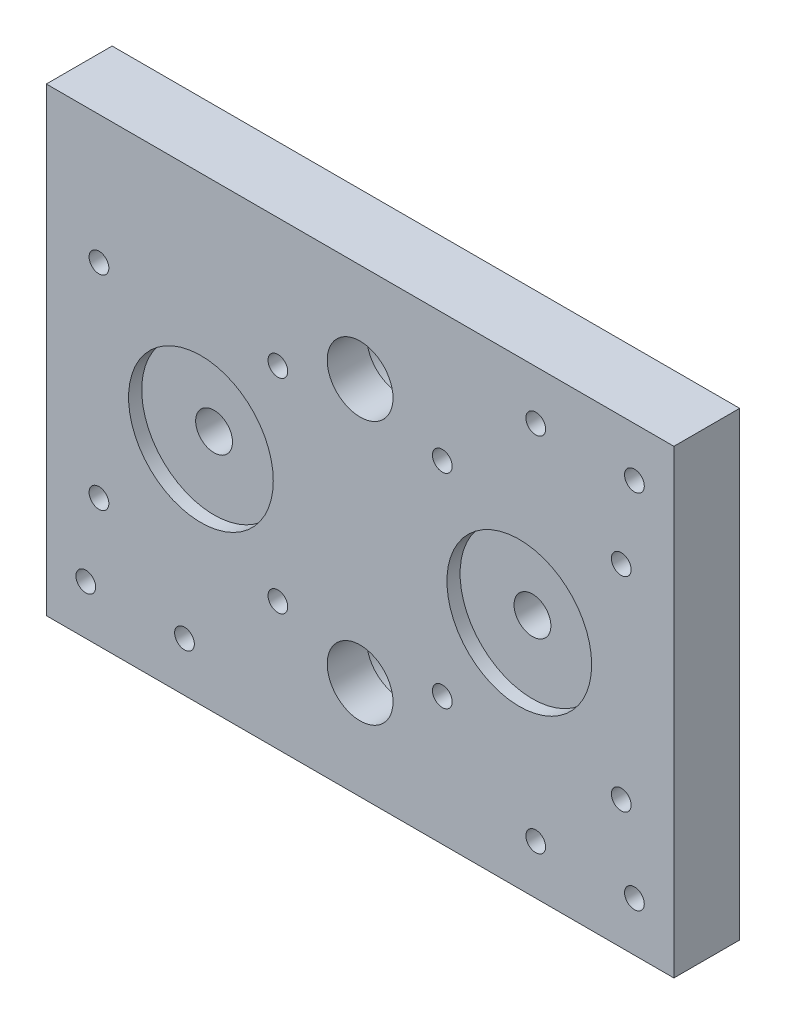
SolidWorks part; units mm, degrees
ref_plane "Front Plane" through (0, 0, 0) normal (0, 0, 1) x (1, 0, 0)
ref_plane "Top Plane" through (0, 0, 0) normal (0, 1, 0) x (1, 0, 0)
ref_plane "Right Plane" through (0, 0, 0) normal (1, 0, 0) x (0, 0, -1)
sketch "Sketch1" plane through (0, 0, 0) normal (0, 0, 1) x (1, 0, 0)
  line L0 (0, 0) -> (0, 40) construction
  line L2 (12.5, -15) -> (-12.5, -15)
  line L3 (12.5, -15) -> (12.5, 55)
  line L4 (12.5, 55) -> (-12.5, 55)
  line L5 (-12.5, -15) -> (-12.5, 55)
  line L6 (12.5, -15) -> (-12.5, 55) construction
  line L7 (12.5, 55) -> (-12.5, -15) construction
  circle A0 centre (0, 40) radius 7.9375
  circle A1 centre (0, 0) radius 7.9375
  point P5 (0, 20)
  dimension "D2" = 15.875
  dimension "D1" = 40
  dimension "D3" = 70
  dimension "D4" = 25
extrude "Boss-Extrude1" add sketch "Sketch1" along normal blind 10
sketch "Sketch2" plane through (0, 0, 10) normal (0, 0, 1) x (1, 0, 0)
  line L0 (12.5, 55) -> (-12.5, 55) construction
  line L1 (-47.7, 55) -> (-8.2, 55)
  line L3 (-47.7, -15) -> (-8.2, -15)
  line L4 (-8.2, 55) -> (-8.2, 36.9142)
  line L5 (-39.7, 35.5) -> (-8.7, 4.5) construction
  line L6 (-39.7, 4.5) -> (-8.7, 35.5) construction
  line L7 (-12.5, -15) -> (12.5, -15) construction
  line L8 (-8.2, 34.0858) -> (-8.2, 5.9142)
  line L9 (0, 55) -> (0, -15) construction
  line L10 (-8.7, 4.5) -> (-39.7, 4.5) construction
  line L11 (-8.7, 4.5) -> (-8.7, 35.5) construction
  line L12 (-8.7, 35.5) -> (-39.7, 35.5) construction
  line L13 (-39.7, 4.5) -> (-39.7, 35.5) construction
  line L14 (-8.7, 4.5) -> (-39.7, 35.5) construction
  line L15 (-8.7, 35.5) -> (-39.7, 4.5) construction
  line L16 (8.7, 35.5) -> (39.7, 4.5) construction
  line L17 (8.7, 4.5) -> (39.7, 35.5) construction
  line L18 (39.7, 4.5) -> (39.7, 35.5) construction
  line L19 (8.7, 35.5) -> (39.7, 35.5) construction
  line L20 (8.7, 4.5) -> (8.7, 35.5) construction
  line L21 (8.7, 4.5) -> (39.7, 4.5) construction
  line L22 (39.7, 4.5) -> (8.7, 35.5) construction
  line L23 (39.7, 35.5) -> (8.7, 4.5) construction
  line L24 (8.2, 55) -> (8.2, 36.9142)
  line L25 (47.7, -15) -> (8.2, -15)
  line L27 (47.7, 55) -> (8.2, 55)
  line L28 (-47.7, 55) -> (-47.7, -15)
  line L29 (47.7, 55) -> (47.7, -15)
  line L31 (-8.2, 3.0858) -> (-8.2, -15)
  line L32 (8.2, 3.0858) -> (8.2, -15)
  line L33 (8.2, 34.0858) -> (8.2, 5.9142)
  circle A0 centre (-39.7, 35.5) radius 1.5
  arc A1 (-8.2, 36.9142) -> (-8.2, 34.0858) centre (-8.7, 35.5) ccw
  arc A2 (-8.2, 5.9142) -> (-8.2, 3.0858) centre (-8.7, 4.5) ccw
  circle A3 centre (-39.7, 4.5) radius 1.5
  circle A4 centre (39.7, 4.5) radius 1.5
  arc A5 (8.2, 5.9142) -> (8.2, 3.0858) centre (8.7, 4.5) cw
  arc A6 (8.2, 36.9142) -> (8.2, 34.0858) centre (8.7, 35.5) cw
  circle A7 centre (39.7, 35.5) radius 1.5
  circle A8 centre (-24.2, 20) radius 2.8
  circle A9 centre (24.2, 20) radius 2.8
  point P0 (-24.2, 20)
  point P11 (-24.2, 20)
  point P34 (24.2, 20)
  dimension "D2" = 3
  dimension "D3" = 5.6
  dimension "D1" = 31
  dimension "D4" = 0.5
  dimension "D5" = 8
  dimension "D6" = 8.2
extrude "Boss-Extrude2" add sketch "Sketch2" against normal up to surface (10 mm away) up to face at (0, 20, 0)
sketch "Sketch6" plane through (0, 0, 10) normal (0, 0, 1) x (1, 0, 0)
  circle A0 centre (-12.5, 35.5) radius 1.5
  circle A1 centre (12.5, 35.5) radius 1.5
  circle A2 centre (-12.5, 4.5) radius 1.5
  circle A3 centre (12.5, 4.5) radius 1.5
  circle A5 centre (-39.7, 35.5) radius 1.5 construction
extrude "Cut-Extrude3" cut sketch "Sketch6" against normal up to surface (10 mm away) up to face at (0, 20, 0)
sketch "Sketch3" plane through (0, 0, 10) normal (0, 0, 1) x (1, 0, 0)
  circle A0 centre (0, 40) radius 7.9375
  circle A1 centre (0, 0) radius 7.9375
  circle A2 centre (0, 40) radius 7.9375 construction
  circle A3 centre (0, 40) radius 5
  circle A4 centre (0, 0) radius 5
  circle A8 centre (0, 0) radius 7.9375 construction
  dimension "D1" = 10
extrude "Boss-Extrude3" add sketch "Sketch3" against normal blind 6.0216
sketch "Sketch4" plane through (0, 0, 10) normal (0, 0, 1) x (1, 0, 0)
  circle A0 centre (-24.2, 20) radius 11
  circle A1 centre (24.2, 20) radius 11
  dimension "D1" = 22
extrude "Cut-Extrude1" cut sketch "Sketch4" against normal blind 2
sketch "Sketch5" plane through (0, 0, 0) normal (0, 0, -1) x (-1, 0, 0)
  circle A0 centre (-39.7, 35.5) radius 2.75
  circle A1 centre (-12.5, 35.5) radius 2.75
  circle A2 centre (-39.7, 4.5) radius 2.75
  circle A3 centre (-12.5, 4.5) radius 2.75
  circle A4 centre (12.5, 35.5) radius 2.75
  circle A5 centre (39.7, 35.5) radius 2.75
  circle A6 centre (12.5, 4.5) radius 2.75
  circle A7 centre (39.7, 4.5) radius 2.75
  circle A9 centre (12.5, 4.5) radius 1.5 construction
  circle A10 centre (-12.5, 4.5) radius 1.5 construction
  circle A11 centre (-12.5, 35.5) radius 1.5 construction
  circle A12 centre (12.5, 35.5) radius 1.5 construction
  dimension "D1" = 5.5
extrude "Cut-Extrude2" cut sketch "Sketch5" against normal blind 3.1
sketch "Sketch11" plane through (0, 0, 0) normal (0, 0, -1) x (-1, 0, 0)
  circle A0 centre (-24.2, 20) radius 10.2
  circle A1 centre (24.2, 20) radius 10.2
  dimension "D1" = 20.4
extrude "Cut-Extrude6" cut sketch "Sketch11" against normal blind 2
sketch "Sketch12" plane through (0, 0, 0) normal (0, 0, -1) x (-1, 0, 0)
  circle A0 centre (24.2, 20) radius 12.5
  dimension "D1" = 25
extrude "Cut-Extrude8" cut sketch "Sketch12" against normal up to surface (2 mm away) up to face at (-34.4, 20, 2)
sketch "Sketch13" plane through (0, 0, 10) normal (0, 0, 1) x (1, 0, 0)
  line L0 (-39.7, 4.5) -> (-41.7, -7.5) construction
  line L1 (-41.7, -7.5) -> (-26.7, -7.5) construction
  line L2 (-26.7, -7.5) -> (-25.8262, -6.2808) construction
  line L3 (25.8262, -6.2808) -> (26.7, -7.5) construction
  line L4 (26.7, -7.5) -> (41.7, -7.5) construction
  line L5 (41.7, -7.5) -> (39.7, 4.5) construction
  line L6 (26.9466, 46.0204) -> (26.7, 47.5) construction
  line L7 (26.7, 47.5) -> (41.7, 47.5) construction
  line L8 (41.7, 47.5) -> (42.5738, 46.2808) construction
  line L9 (-47.7, 55) -> (-47.7, -15) construction
  line L10 (47.7, -15) -> (47.7, 55) construction
  circle A0 centre (-41.7, -7.5) radius 1.5
  circle A1 centre (-26.7, -7.5) radius 1.5
  circle A2 centre (26.7, -7.5) radius 1.5
  circle A3 centre (41.7, -7.5) radius 1.5
  circle A4 centre (26.7, 47.5) radius 1.5
  circle A5 centre (41.7, 47.5) radius 1.5
  point P14 (0, 0)
  point P19 (0, 0)
  point P24 (0, 0)
  point P28 (0, 0)
  dimension "D1" = 3
  dimension "D2" = 15
  dimension "D3" = 15
  dimension "D4" = 12
  dimension "D5" = 6
  dimension "D6" = 6
  dimension "D7" = 55
extrude "Cut-Extrude9" cut sketch "Sketch13" against normal up to surface (10 mm away) up to face at (-36.7, 20, 0)
